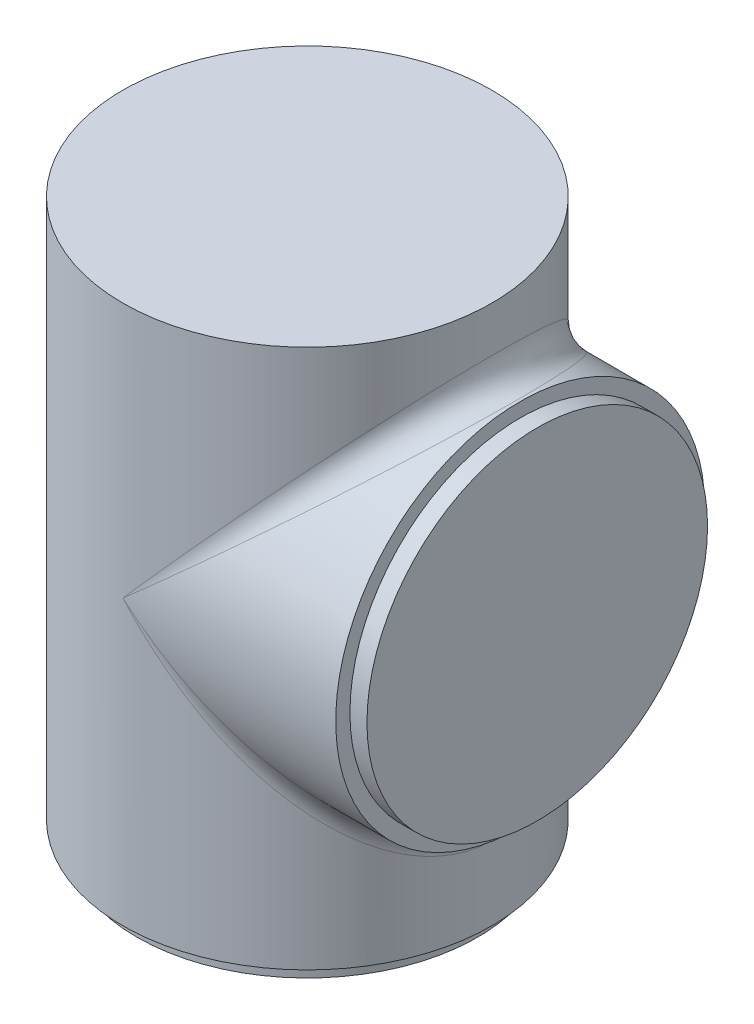
SolidWorks part; units mm, degrees
material "PP Copolymer"
ref_plane "Front Plane" through (0, 0, 0) normal (0, 0, 1) x (1, 0, 0)
ref_plane "Top Plane" through (0, 0, 0) normal (0, 1, 0) x (1, 0, 0)
ref_plane "Right Plane" through (0, 0, 0) normal (1, 0, 0) x (0, 0, -1)
sketch "Sketch1" plane through (0, 0, 0) normal (0, 1, 0) x (1, 0, 0)
  circle A0 centre (0, 0) radius 30
  dimension "D1" = 60
extrude "Boss-Extrude1" add sketch "Sketch1" along normal blind 3
sketch "Sketch2" plane through (0, 3, 0) normal (0, 1, 0) x (1, 0, 0)
  circle A0 centre (0, 0) radius 32.5
  dimension "D1" = 65
extrude "Boss-Extrude2" add sketch "Sketch2" along normal blind 85
sketch "Sketch3" plane through (0, 0, 0) normal (1, 0, 0) x (0, 0, -1)
  line L0 (-32.5, 43) -> (32.5, 43) construction
  line L1 (-32.5, 88) -> (-32.5, 3) construction
  line L2 (32.5, 3) -> (32.5, 88) construction
  line L3 (-30, 3) -> (30, 3) construction
  circle A0 centre (0, 43) radius 32.5
  dimension "D2" = 65
  dimension "D1" = 40
extrude "Boss-Extrude3" add sketch "Sketch3" along normal blind 37.5 contours A0
fillet "Fillet1" radius 4.5 2 edges at (32.5, 75.5, 0) (32.5, 10.5, 0)
sketch "Sketch5" plane through (37.5, 0, 0) normal (1, 0, 0) x (0, 0, -1)
  circle A0 centre (0, 43) radius 30
  dimension "D1" = 60
extrude "Boss-Extrude5" add sketch "Sketch5" along normal blind 3
sketch "Sketch6" plane through (0, 3, 0) normal (0, -1, 0) x (1, 0, 0)
  circle A0 centre (0, 0) radius 32.5 construction
  circle A1 centre (0, 0) radius 32.5
extrude "Boss-Extrude6" add sketch "Sketch6" along normal blind 10
sketch "Sketch8" plane through (0, -7, 0) normal (0, -1, 0) x (1, 0, 0)
  circle A0 centre (0, 0) radius 30
  dimension "D1" = 60
extrude "Boss-Extrude8" add sketch "Sketch8" along normal blind 3
